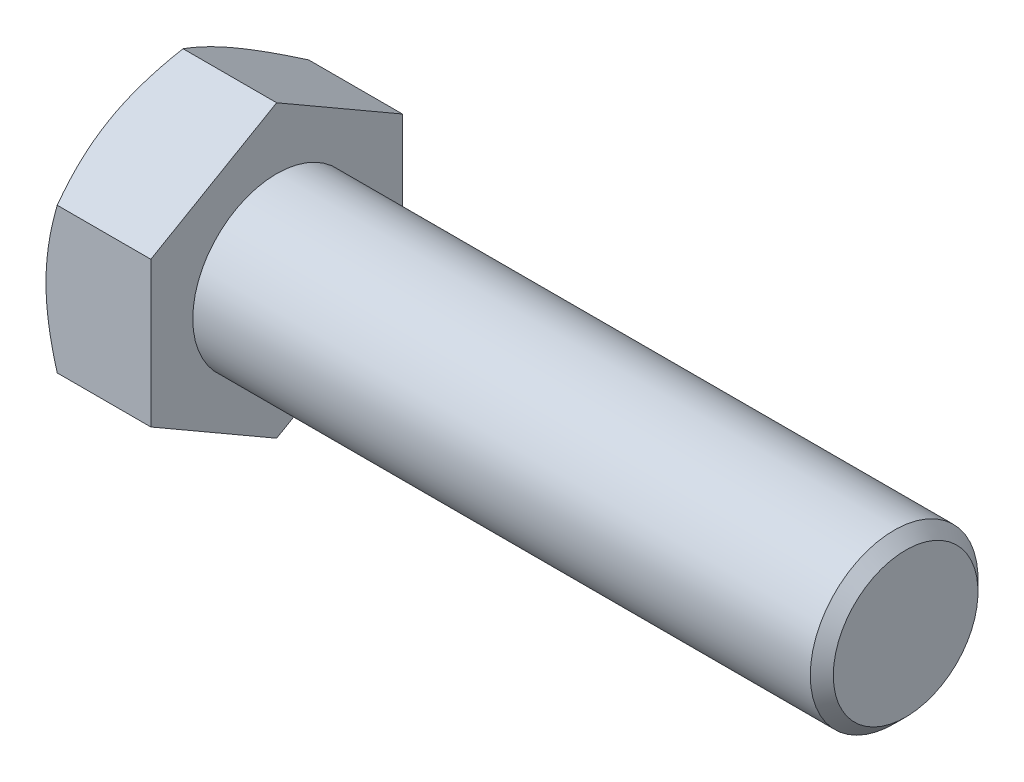
SolidWorks part; units mm, degrees
ref_plane "Front Plane" through (0, 0, 0) normal (0, 0, 1) x (1, 0, 0)
ref_plane "Top Plane" through (0, 0, 0) normal (0, 1, 0) x (1, 0, 0)
ref_plane "Right Plane" through (0, 0, 0) normal (1, 0, 0) x (0, 0, -1)
sketch "BaseHeadSke" plane through (0, 0, 0) normal (1, 0, 0) x (0, 0, -1)
  line L1 (0, 20.7846) -> (-18, 10.3923)
  line L2 (-18, 10.3923) -> (-18, -10.3923)
  line L3 (-18, -10.3923) -> (0, -20.7846)
  line L4 (0, -20.7846) -> (18, -10.3923)
  line L5 (18, -10.3923) -> (18, 10.3923)
  line L6 (18, 10.3923) -> (0, 20.7846)
  circle A0 centre (0, 0) radius 18 construction
extrude "BaseHead" add sketch "BaseHeadSke" along normal blind 15
sketch "HeadChamferSke" plane through (0, 0, 0) normal (0, 0, 1) x (1, 0, 0)
  line L0 (0, 0) -> (59.4924, 0) construction
  line L1 (0, 10.3923) -> (0, -10.3923) construction
  line L2 (0, 20.7846) -> (0, 18)
  line L3 (0, 18) -> (1.6077, 20.7846)
  line L4 (1.6077, 20.7846) -> (0, 20.7846)
  line L7 (15, 20.7846) -> (0, 20.7846) construction
  dimension "Angle_Chamfer_Head" = 30
revolve "HeadChamfer" cut sketch "HeadChamferSke" angle 360 about L0
sketch "BodySke" plane through (0, 0, 0) normal (0, 0, 1) x (1, 0, 0)
  line L0 (0, 0) -> (134.9018, 0) construction
  line L1 (0, 0) -> (0, 12)
  line L2 (0, 12) -> (103.352, 12)
  line L3 (105, 10.352) -> (105, 0)
  line L4 (105, 0) -> (0, 0)
  line L5 (15, 10.3923) -> (15, -10.3923) construction
  line L6 (103.352, 12) -> (105, 10.352)
  line L7 (18, 0) -> (18, 20.3478) construction
  dimension "Thread_minor" = 20.704
  dimension "Advance" = 3
revolve "BaseBody" add sketch "BodySke" angle 360 about L0
cosmetic thread "ThreadCosmetic" [suppressed] parameters "Thread_minor"=20.704
sketch "BearingFaceSke" plane through (0, 0, 0) normal (0, 0, 1) x (1, 0, 0)
  line L0 (0, 0) -> (129.635, 0) construction
  line L1 (15, 20.7846) -> (15, 10.3923) construction
  line L2 (15, 18) -> (14.2, 18)
  line L3 (15, 18) -> (15, 28)
  line L4 (15, 28) -> (14.2, 28)
  line L5 (14.2, 18) -> (14.2, 28)
  dimension "D1" = 10
  dimension "D2" = 36
revolve "BearingFace" [suppressed] cut sketch "BearingFaceSke" angle 360 about L0
fillet "HeadFillet" [suppressed] radius 0.8
sketch "ThdSchSke" plane through (0, 0, 0) normal (0, 0, 1) x (1, 0, 0)
  line L0 (0, 0) -> (122.6446, 0) construction
  line L1 (100.352, 13.9029) -> (100.352, 12)
  line L2 (100.352, 13.9029) -> (102.2549, 13.9029)
  line L3 (102.2549, 13.9029) -> (102.2549, 12)
  line L4 (102.2549, 12) -> (101.3035, 10.352)
  line L5 (101.3035, 10.352) -> (100.352, 12)
  dimension "D1" = 3
revolve "ThreadSchematic" [suppressed] cut sketch "ThdSchSke" angle 360 about L0
pattern_linear "ThdSchPat" [suppressed] of bodies 117
equation "\"Thread_minor@ThreadCosmetic\" = \"Thread_minor@BodySke\""
equation "\"D2@BearingFaceSke\" = \"Width_flats@BaseHeadSke\""
equation "\"D1@ThdSchSke\" = \"Advance@BodySke\""
equation "\"Advance@ThdSchPat\" = \"Advance@BodySke\""
equation "\"Tooth_Num@ThdSchPat\" =  int( \"Length@BodySke\" / \"Advance@BodySke\" )  - 1"
